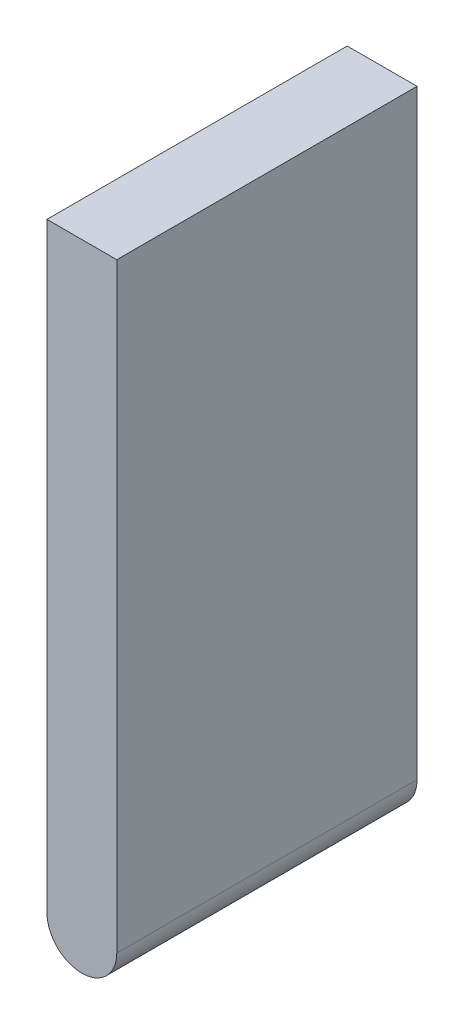
SolidWorks part; units mm, degrees
ref_plane "Front Plane" through (0, 0, 0) normal (0, 0, 1) x (1, 0, 0)
ref_plane "Top Plane" through (0, 0, 0) normal (0, 1, 0) x (1, 0, 0)
ref_plane "Right Plane" through (0, 0, 0) normal (1, 0, 0) x (0, 0, -1)
sketch "Sketch1" plane through (0, 0, 0) normal (0, 0, 1) x (1, 0, 0)
  circle A0 centre (0, 0) radius 75
  dimension "D1" = 150
extrude "Boss-Extrude1" add sketch "Sketch1" along normal blind 645
sketch "Sketch2" plane through (0, 0, 0) normal (0, 1, 0) x (1, 0, 0)
  line L1 (-75, 0) -> (75, 0)
  line L2 (-75, 0) -> (-75, -645)
  line L3 (-75, -645) -> (75, -645)
  line L4 (75, 0) -> (75, -645)
extrude "Boss-Extrude2" add sketch "Sketch2" along normal blind 1290
